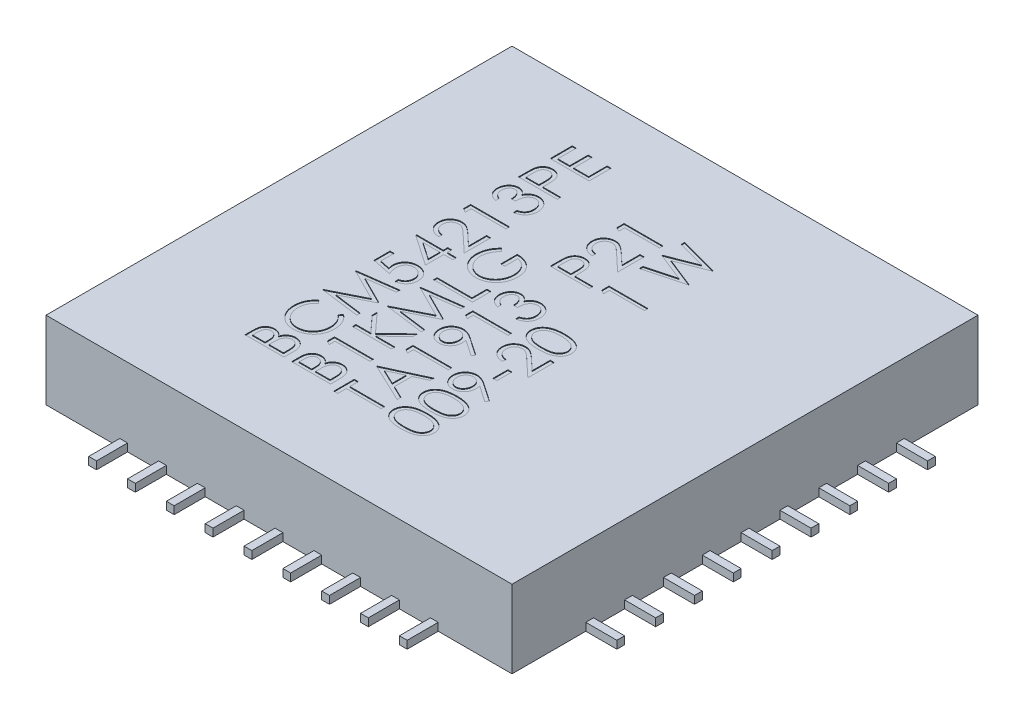
SolidWorks part; units mm, degrees
ref_plane "Front Plane" through (0, 0, 0) normal (0, 0, 1) x (1, 0, 0)
ref_plane "Top Plane" through (0, 0, 0) normal (0, 1, 0) x (1, 0, 0)
ref_plane "Right Plane" through (0, 0, 0) normal (1, 0, 0) x (0, 0, -1)
sketch "BaseS" plane through (0, 0, 0) normal (0, 1, 0) x (1, 0, 0)
  line L1 (-3, 3) -> (3, 3)
  line L2 (-3, 3) -> (-3, -3)
  line L3 (-3, -3) -> (3, -3)
  line L4 (3, 3) -> (3, -3)
  line L5 (-3, 3) -> (3, -3) construction
  line L6 (-3, -3) -> (3, 3) construction
  point P0 (0, 0)
  dimension "W" = 6
  dimension "L" = 6
extrude "Base" add sketch "BaseS" along normal blind 1
sketch "SolderConnectionS" plane through (0, 0, 0) normal (0, 1, 0) x (1, 0, 0)
  line L0 (3, -2) -> (3.4, -2)
  line L1 (3, -3) -> (3, 3) construction
  dimension "XDim" = 1
  dimension "Length" = 0.4
extrude "SolderConnection" add sketch "SolderConnectionS" along normal blind 0.1 thin thin type mid plane wall 0.1
pattern_linear "SC LP" count 9 spacing 0.5 along (0, 0, -1) of "SolderConnection"
ref_axis "AxisSC" through (0, 0.84, 0) along (0, -1, 0)
pattern_circular "SC CP" count 4 over 360 about axis through (0, 0.84, 0) along (0, -1, 0) of "SolderConnection", "SC LP"
sketch "PartNoS" plane through (0, 1, 0) normal (0, 1, 0) x (1, 0, 0)
  line L0 (-1, -2) -> (-1, 3) construction
  line L1 (3, 3) -> (-3, 3) construction
  line L2 (-3, -3) -> (3, -3) construction
  line L3 (-3, 3) -> (-3, -3) construction
  line L5 (-0.4, -2) -> (-0.4, 3) construction
  line L6 (0.2, -2) -> (0.2, 3) construction
  line L7 (0.8, -2) -> (0.8, 3) construction
  line L8 (-1, -2) -> (-0.4, -2) construction
  line L9 (-0.4, -2) -> (0.2, -2) construction
  line L10 (0.2, -2) -> (0.8, -2) construction
  text T0 "BCM54213PE" font "Century Gothic" height 0.5
  dimension "YDim" = 2
  dimension "XDim" = 1
  dimension "YDist" = 0.6
extrude "PartNo" cut sketch "PartNoS" against normal blind 0.01
sketch "PartNoSE1" plane through (0, 1, 0) normal (0, 1, 0) x (1, 0, 0)
  text T0 "B1KMLG" font "Century Gothic" height 0.5
sketch "PartNoSE2" plane through (0, 1, 0) normal (0, 1, 0) x (1, 0, 0)
  text T0 "TA1913  P21" font "Century Gothic" height 0.5
sketch "PartNoSE3" plane through (0, 1, 0) normal (0, 1, 0) x (1, 0, 0)
  text T0 "009-20   1 W" font "Century Gothic" height 0.5
extrude "PartNoE1" cut sketch "PartNoSE1" against normal up to surface (0.01 mm away) up to face at (-1.1429, 0.99, 1.8178)
extrude "PartNoE2" cut sketch "PartNoSE2" against normal up to surface (0.01 mm away) up to face at (-1.1429, 0.99, 1.8178)
extrude "PartNoE3" cut sketch "PartNoSE3" against normal up to surface (0.01 mm away) up to face at (-1.1429, 0.99, 1.8178)
